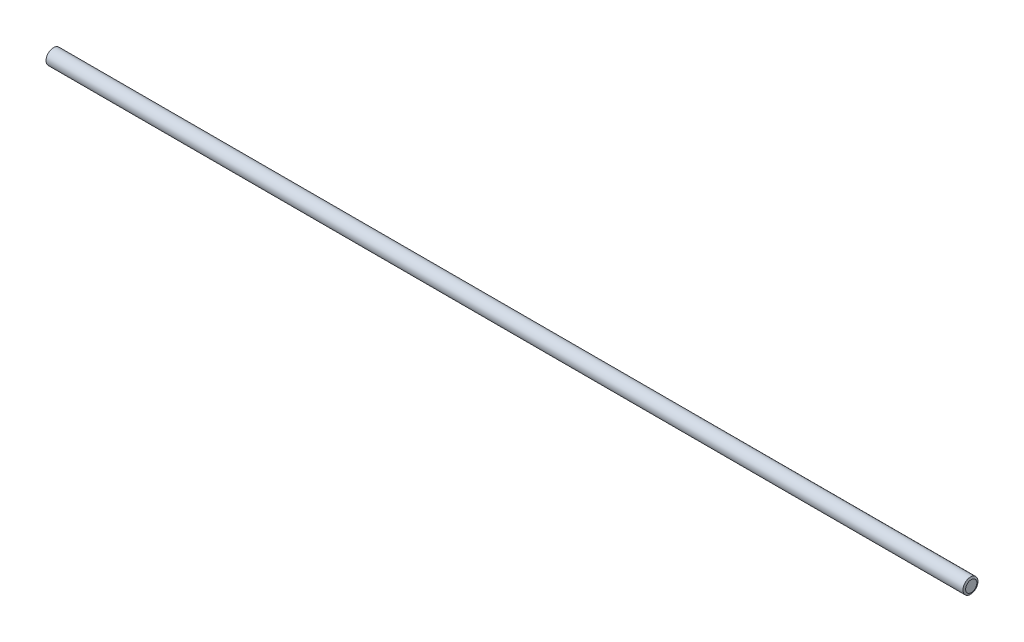
SolidWorks part; units mm, degrees
material "Alloy Steel"
ref_plane "Front Plane" through (0, 0, 0) normal (0, 0, 1) x (1, 0, 0)
ref_plane "Top Plane" through (0, 0, 0) normal (0, 1, 0) x (1, 0, 0)
ref_plane "Right Plane" through (0, 0, 0) normal (1, 0, 0) x (0, 0, -1)
ref_plane "Plane1" through (0, 0, 0) normal (0, 0, 1) x (1, 0, 0)
sketch "Sketch1" plane through (0, 0, 0) normal (0, 0, 1) x (1, 0, 0)
  line L0 (0, 0) -> (0, 3.7369)
  line L1 (0, 3.7369) -> (0.5, 5)
  line L2 (0.5, 5) -> (609.5, 5)
  line L3 (609.5, 5) -> (610, 3.7369)
  line L4 (610, 3.7369) -> (610, 0)
  line L5 (610, 0) -> (0, 0)
  line L6 (610, 0) -> (0, 0) construction
  line L7 (305, 0) -> (305, 5) construction
  dimension "D1" = 610
  dimension "D2" = 21.597
  dimension "D3" = 5
  dimension "D4" = 1.2631
  dimension "D5" = 21.597
revolve "Revolve1" add sketch "Sketch1" angle 360 about L6 reverse direction yes
